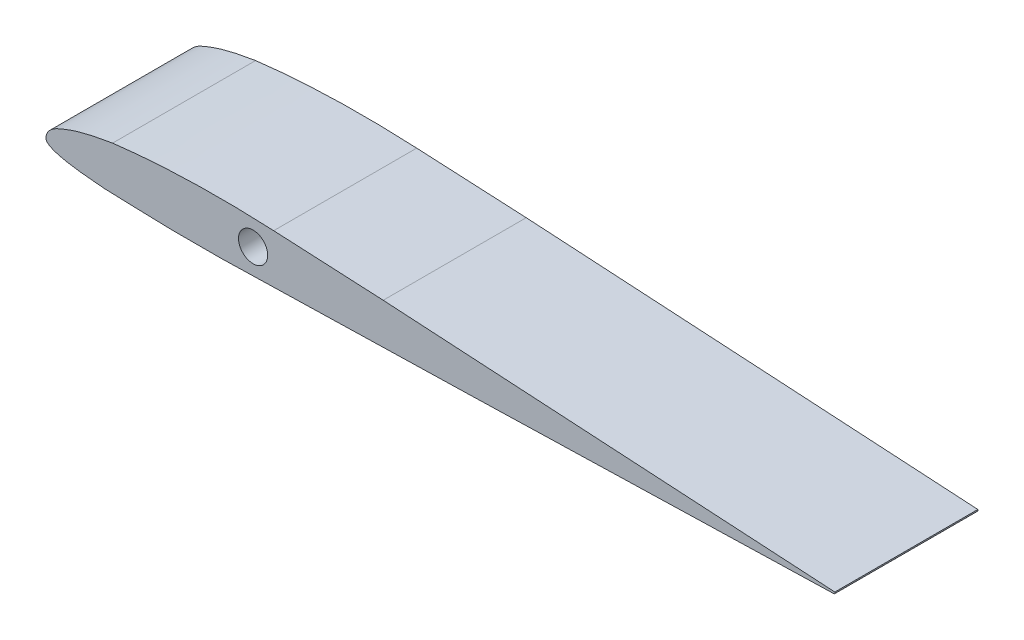
SolidWorks part; units mm, degrees
material "Polyurethane Foam Flexible"
ref_plane "Front Plane" through (0, 0, 0) normal (0, 0, 1) x (1, 0, 0)
ref_plane "Top Plane" through (0, 0, 0) normal (0, 1, 0) x (1, 0, 0)
ref_plane "Right Plane" through (0, 0, 0) normal (1, 0, 0) x (0, 0, -1)
sketch "Sketch3" plane through (0, 0, 0) normal (0, 0, 1) x (1, 0, 0)
  line L0 (202.9941, 8.6587) -> (110.5837, 6.1553)
  line L1 (110.5837, 6.1553) -> (45.2437, 4.5477)
  line L2 (58.6413, 17.491) -> (86.8465, 16.0766)
  line L3 (0, 35.3471) -> (0, -15.2378) construction
  line L4 (86.8465, 16.0766) -> (160.9786, 11.667)
  line L5 (160.9786, 11.667) -> (203.1607, 9.1578)
  line L6 (203.1999, 14.8061) -> (203.1999, -9.9364) construction
  line L7 (0, 0) -> (203.1999, 0) construction
  line L8 (50.8, 72.9775) -> (50.8, -63.9956) construction
  arc A0 (203.1607, 9.1578) -> (202.9941, 8.6587) centre (202.8278, 8.9915) cw
  spline S0 degree 3 poles (45.2437, 4.5477) (38.9236, 4.5689) (32.5987, 4.4374) (26.2837, 4.6938) (22.3484, 4.8536) (18.4102, 4.9373) (14.4749, 5.0971) (14.4129, 5.0996) (14.3701, 5.1734) (14.3085, 5.1801) (13.7572, 5.24) (0.0923, 5.9331) (0.0016, 8.7406) (-0.0833, 11.3694) (3.2406, 12.5979) (5.1525, 13.3198) (6.7026, 13.905) (8.2818, 14.4263) (9.8909, 14.8216) (12.2626, 15.4044) (14.6912, 15.8835) (17.1496, 16.275) knots 0 0 0 0 1 1 1 2 2 2 3 3 3 4 4 4 5 5 5 6 6 6 6.272168 6.272168 6.272168 6.272168
  spline S1 degree 3 poles (17.1496, 16.275) (28.8325, 17.7257) (42.6703, 18.2919) (58.6413, 17.491) knots 0 0 0 0 1 1 1 1
  point P17 (50.8, 17.7806)
  point P18 (50.8, 4.6844)
  dimension "D1" = 203.1999
  dimension "D2" = 50.8
extrude "Airfoil" add sketch "Sketch3" along normal blind 36.83
sketch "Sketch8" plane through (0, 0, 0) normal (0, 0, -1) x (-1, 0, 0)
  line L0 (0, 16.6795) -> (0, -1.637) construction
  line L1 (-203.1999, 12.5809) -> (-203.1999, 6.3994) construction
  line L2 (-53.34, 11.2284) -> (-53.34, 17.7099) construction
  line L3 (-53.34, 11.2284) -> (-53.34, 4.7469) construction
  line L4 (-45.2437, 4.5477) -> (-110.5837, 6.1553) construction
  circle A0 centre (-53.34, 11.2284) radius 3.7592
  arc A1 (-203.1607, 9.1578) -> (-202.9941, 8.6587) centre (-202.8278, 8.9915) ccw construction
  spline S0 degree 3 poles (-17.1496, 16.275) (-14.6912, 15.8835) (-12.2626, 15.4044) (-9.8909, 14.8216) (-8.2818, 14.4263) (-6.7026, 13.905) (-5.1525, 13.3198) (-3.2406, 12.5979) (0.0833, 11.3694) (-0.0016, 8.7406) (-0.0923, 5.9331) (-13.7572, 5.24) (-14.3085, 5.1801) (-14.3701, 5.1734) (-14.4129, 5.0996) (-14.4749, 5.0971) (-18.4102, 4.9373) (-22.3484, 4.8536) (-26.2837, 4.6938) (-32.5987, 4.4374) (-38.9236, 4.5689) (-45.2437, 4.5477) knots 0 0 0 0 0.272168 0.272168 0.272168 1.272168 1.272168 1.272168 2.272168 2.272168 2.272168 3.272168 3.272168 3.272168 4.272168 4.272168 4.272168 5.272168 5.272168 5.272168 6.272168 6.272168 6.272168 6.272168 construction
  spline S1 degree 3 poles (-58.6413, 17.491) (-42.6703, 18.2919) (-28.8325, 17.7257) (-17.1496, 16.275) knots 0 0 0 0 1 1 1 1 construction
  dimension "D1" = 7.5184
  dimension "D2" = 53.34
extrude "Camera Channel" cut sketch "Sketch8" against normal up to next
